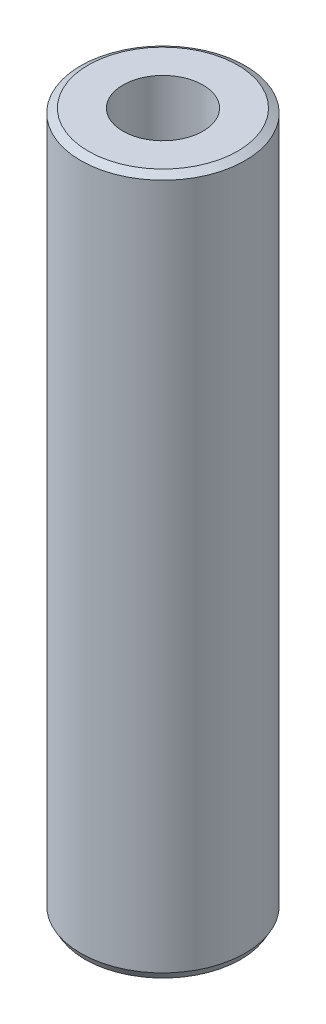
SolidWorks part; units mm, degrees
ref_plane "Front Plane" through (0, 0, 0) normal (0, 0, 1) x (1, 0, 0)
ref_plane "Top Plane" through (0, 0, 0) normal (0, 1, 0) x (1, 0, 0)
ref_plane "Right Plane" through (0, 0, 0) normal (1, 0, 0) x (0, 0, -1)
sketch "Sketch1" plane through (0, 0, 0) normal (0, 1, 0) x (1, 0, 0)
  circle A0 centre (0, 0) radius 10
  dimension "SHAFT_OD" = 20
extrude "Boss-Extrude1" add sketch "Sketch1" along normal blind 84.9295
sketch "Sketch2" plane through (0, 0, 0) normal (0, 1, 0) x (1, 0, 0)
  circle A0 centre (0, 0) radius 4.8698
  dimension "BORE_D" = 9.7396
extrude "Cut-Extrude1" cut sketch "Sketch2" along normal through all
chamfer "Chamfer1" distance 0.5305 angle 60 2 edges at (0, 84.9295, 10) (0, 0, 10) first distance on face at (0, 84.9295, 10) first distance on face at (0, 0, 4.8698)
